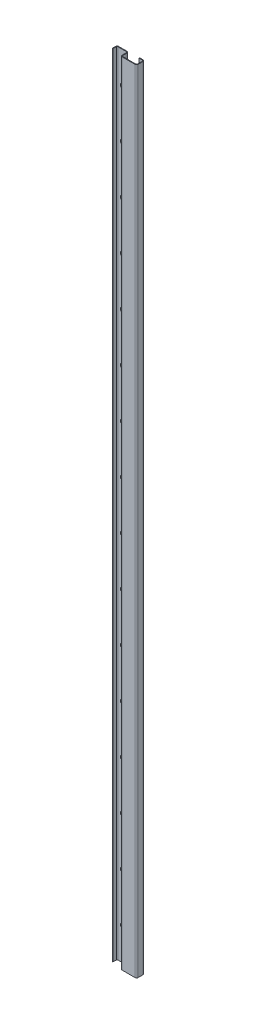
SolidWorks part; units mm, degrees
note: The reader was unsure of these and kept them because the rebuilt part matched: flange length of "Edge-Flange1", "Edge-Flange2", "Edge-Flange3", "Edge-Flange4", "Edge-Flange5".
material "Galvanized Steel"
ref_plane "Front Plane" through (0, 0, 0) normal (0, 0, 1) x (1, 0, 0)
ref_plane "Top Plane" through (0, 0, 0) normal (0, 1, 0) x (1, 0, 0)
ref_plane "Right Plane" through (0, 0, 0) normal (1, 0, 0) x (0, 0, -1)
sketch "Sketch1" plane through (0, 0, 0) normal (0, 0, 1) x (1, 0, 0)
  line L1 (18, -1240) -> (-18, -1240)
  line L2 (18, -1240) -> (18, 1240)
  line L3 (18, 1240) -> (-18, 1240)
  line L4 (-18, -1240) -> (-18, 1240)
  line L5 (18, -1240) -> (-18, 1240) construction
  line L6 (18, 1240) -> (-18, -1240) construction
  point P0 (0, 0)
  dimension "D1" = 2480
  dimension "D2" = 36
base flange "Base-Flange1" sketch "Sketch1" thickness 2 reverse thickness direction no parameters "D1"=8
edge flange "Edge-Flange1" sketch "Sketch8" flange angle 90 flange length 15 flange position material inside bend radius 2.5 thickness 2 relief rectangular parameters "D6"=10
sketch "Sketch8" plane through (-18, 0, 0) normal (-1, 0, 0) x (0, -1, 0)
  line L2 (-1240, 0) -> (-1240, 13)
  line L3 (-1240, 13) -> (1240, 13)
  line L4 (1240, 13) -> (1240, 0)
  line L7 (-1240, 0) -> (1240, 0) construction
  line L8 (-1240, 0) -> (1240, 0)
bend "EdgeBend1" bend radius 2.5 bend angle 90 parameters "D5"=1
edge flange "Edge-Flange2" sketch "Sketch11" flange angle 90 flange length 23 flange position material inside bend radius 2.5 thickness 2 parameters "D6"=10
sketch "Sketch11" plane through (18, 0, 0) normal (1, 0, 0) x (0, 1, 0)
  line L0 (-1240, 0) -> (1240, 0) construction
  line L1 (-1240, 0) -> (1240, 0)
  line L2 (-1240, 0) -> (-1240, 21)
  line L3 (-1240, 21) -> (1240, 21)
  line L4 (1240, 21) -> (1240, 0)
bend "EdgeBend2" bend radius 2.5 bend angle 90 parameters "D5"=2
edge flange "Edge-Flange3" sketch "Sketch14" flange angle 90 flange length 50 flange position material inside bend radius 2.5 thickness 2 relief rectangular parameters "D6"=10
sketch "Sketch14" plane through (18, 0, 21) normal (0, 0, 1) x (0, -1, 0)
  line L2 (-1240, 0) -> (-1240, 48)
  line L3 (-1240, 48) -> (1240, 48)
  line L4 (1240, 48) -> (1240, 0)
  line L7 (-1240, 0) -> (1240, 0) construction
  line L8 (-1240, 0) -> (1240, 0)
bend "EdgeBend3" bend radius 2.5 bend angle 90 parameters "D5"=3
edge flange "Edge-Flange4" sketch "Sketch17" flange angle 90 flange length 25 flange position material inside bend radius 2.5 thickness 2 relief rectangular parameters "D6"=10
sketch "Sketch17" plane through (66, 0, 19) normal (-1, 0, 0) x (0, 1, 0)
  line L2 (-1240, 0) -> (-1240, 23)
  line L3 (-1240, 23) -> (1240, 23)
  line L4 (1240, 23) -> (1240, 0)
  line L5 (1240, 0) -> (-1240, 0) construction
  line L6 (1240, 0) -> (-1240, 0)
bend "EdgeBend4" bend radius 2.5 bend angle 90 parameters "D5"=4
edge flange "Edge-Flange5" sketch "Sketch20" flange angle 90 flange length 15 flange position material inside bend radius 2.5 thickness 2 relief rectangular parameters "D6"=10
sketch "Sketch20" plane through (64, 0, -4) normal (0, 0, 1) x (0, 1, 0)
  line L2 (-1240, 0) -> (-1240, 13)
  line L3 (-1240, 13) -> (1240, 13)
  line L4 (1240, 13) -> (1240, 0)
  line L5 (1240, 0) -> (-1240, 0) construction
  line L6 (1240, 0) -> (-1240, 0)
bend "EdgeBend5" bend radius 2.5 bend angle 90 parameters "D5"=5
sketch "Sketch21" plane through (0, 0, 0) normal (0, 0, 1) x (1, 0, 0)
  line L0 (-18, -1240) -> (-18, 1240) construction
  line L1 (13.5, 1240) -> (-13.5, 1240) construction
  circle A0 centre (0, 1140) radius 6
  dimension "D1" = 12
  dimension "D2" = 18
  dimension "D3" = 100
extrude "Cut-Extrude1" cut sketch "Sketch21" against normal blind 10 normal cut yes
pattern_linear "LPattern1" count 16 spacing 152 along (0, -1, 0) of "Cut-Extrude1"
sketch "Bend-Lines1" [suppressed] plane through (0, 0, 0) normal (0, 1, 0) x (1, 0, 0)
sketch "Bounding-Box1" [suppressed] plane through (0, 0, 0) normal (0, 1, 0) x (1, 0, 0)
sheet metal parameters "Sheet-Metal8" thickness 2 parameters "D1"=8
flat pattern "Flat-Pattern8" [suppressed]
sketch "Bend-Lines2" plane through (0, 0, 0) normal (0, 1, 0) x (1, 0, 0)
sketch3d "Bounding-Box2" [suppressed]
  line L0 (-18, 1214, 0) -> (-18, -1214, 0) construction
  line L1 (18, 1214, 0) -> (18, -1214, 0) construction
  line L2 (-18, 1214, 0) -> (18, 1214, 0) construction
  line L3 (-18, -1214, 0) -> (18, -1214, 0) construction
sheet metal parameters "Sheet-Metal9" thickness 2 parameters "D1"=8
flat pattern "Flat-Pattern8"
sketch "Bend-Lines2" plane through (0, 0, 0) normal (0, 0, 1) x (1, 0, 0)
  line L0 (-16.2489, 1214) -> (-16.2489, -1214) construction
  line L1 (-16.2489, 1214) -> (-16.2489, -1214) construction
sketch3d "Bounding-Box2" [suppressed]
  line L0 (18, 1214, 0) -> (18, -1214, 0) construction
  line L1 (-29.4978, 1214, 0) -> (-29.4978, -1214, 0) construction
  line L2 (18, 1214, 0) -> (-29.4978, 1214, 0) construction
  line L3 (18, -1214, 0) -> (-29.4978, -1214, 0) construction
bend of the flat pattern "Flatten-<EdgeBend1>1"
sheet metal parameters "Sheet-Metal10" thickness 2 parameters "D1"=8
flat pattern "Flat-Pattern8"
sketch "Bend-Lines2" plane through (0, 0, 0) normal (0, 0, 1) x (1, 0, 0)
  line L0 (-16.2489, 1214) -> (-16.2489, -1214) construction
  line L1 (-16.2489, 1214) -> (-16.2489, -1214) construction
  line L2 (15.0686, -1214) -> (15.0686, 1214) construction
  line L3 (15.0686, -1214) -> (15.0686, 1214) construction
sketch3d "Bounding-Box2" [suppressed]
  line L0 (37.1372, 1214, 0) -> (37.1372, -1214, 0) construction
  line L1 (-29.4978, 1214, 0) -> (-29.4978, -1214, 0) construction
  line L2 (37.1372, 1214, 0) -> (-29.4978, 1214, 0) construction
  line L3 (37.1372, -1214, 0) -> (-29.4978, -1214, 0) construction
bend of the flat pattern "Flatten-<EdgeBend1>1"
bend of the flat pattern "Flatten-<EdgeBend2>1"
sheet metal parameters "Sheet-Metal11" thickness 2 parameters "D1"=8
flat pattern "Flat-Pattern8"
sketch "Bend-Lines2" plane through (0, 0, 0) normal (0, 0, 1) x (1, 0, 0)
  line L0 (-16.2489, 1214) -> (-16.2489, -1214) construction
  line L1 (-16.2489, 1214) -> (-16.2489, -1214) construction
  line L2 (15.0686, -1214) -> (15.0686, 1214) construction
  line L3 (15.0686, -1214) -> (15.0686, 1214) construction
  line L4 (35.3861, -1214) -> (35.3861, 1214) construction
  line L5 (35.3861, -1214) -> (35.3861, 1214) construction
sketch3d "Bounding-Box2" [suppressed]
  line L0 (83.635, 1214, 0) -> (83.635, -1214, 0) construction
  line L1 (-29.4978, 1214, 0) -> (-29.4978, -1214, 0) construction
  line L2 (83.635, 1214, 0) -> (-29.4978, 1214, 0) construction
  line L3 (83.635, -1214, 0) -> (-29.4978, -1214, 0) construction
bend of the flat pattern "Flatten-<EdgeBend1>1"
bend of the flat pattern "Flatten-<EdgeBend2>1"
bend of the flat pattern "Flatten-<EdgeBend3>1"
sheet metal parameters "Sheet-Metal12" thickness 2 parameters "D1"=8
flat pattern "Flat-Pattern8"
sketch "Bend-Lines2" plane through (0, 0, 0) normal (0, 0, 1) x (1, 0, 0)
  line L0 (-16.2489, 1214) -> (-16.2489, -1214) construction
  line L1 (-16.2489, 1214) -> (-16.2489, -1214) construction
  line L2 (15.0686, -1214) -> (15.0686, 1214) construction
  line L3 (15.0686, -1214) -> (15.0686, 1214) construction
  line L4 (35.3861, -1214) -> (35.3861, 1214) construction
  line L5 (35.3861, -1214) -> (35.3861, 1214) construction
  line L6 (81.8838, -1214) -> (81.8838, 1214) construction
  line L7 (81.8838, -1214) -> (81.8838, 1214) construction
sketch3d "Bounding-Box2" [suppressed]
  line L0 (105.1327, 1214, 0) -> (105.1327, -1214, 0) construction
  line L1 (-29.4978, 1214, 0) -> (-29.4978, -1214, 0) construction
  line L2 (105.1327, 1214, 0) -> (-29.4978, 1214, 0) construction
  line L3 (105.1327, -1214, 0) -> (-29.4978, -1214, 0) construction
bend of the flat pattern "Flatten-<EdgeBend1>1"
bend of the flat pattern "Flatten-<EdgeBend2>1"
bend of the flat pattern "Flatten-<EdgeBend3>1"
bend of the flat pattern "Flatten-<EdgeBend4>1"
sheet metal parameters "Sheet-Metal13" thickness 2 parameters "D1"=8
flat pattern "Flat-Pattern8"
sketch "Bend-Lines2" plane through (0, 0, 0) normal (0, 0, 1) x (1, 0, 0)
  line L0 (-16.2489, 1210) -> (-16.2489, -1210) construction
  line L1 (-16.2489, 1210) -> (-16.2489, -1210) construction
  line L2 (16.2489, -1210) -> (16.2489, 1210) construction
  line L3 (16.2489, -1210) -> (16.2489, 1210) construction
  line L4 (35.7467, -1210) -> (35.7467, 1210) construction
  line L5 (35.7467, -1210) -> (35.7467, 1210) construction
  line L6 (82.2445, -1210) -> (82.2445, 1210) construction
  line L7 (82.2445, -1210) -> (82.2445, 1210) construction
  line L8 (103.7423, -1210) -> (103.7423, 1210) construction
  line L9 (103.7423, -1210) -> (103.7423, 1210) construction
sketch3d "Bounding-Box2" [suppressed]
  line L0 (116.9911, 1210, 0) -> (116.9911, -1210, 0) construction
  line L1 (-29.4978, 1210, 0) -> (-29.4978, -1210, 0) construction
  line L2 (116.9911, 1210, 0) -> (-29.4978, 1210, 0) construction
  line L3 (116.9911, -1210, 0) -> (-29.4978, -1210, 0) construction
bend of the flat pattern "Flatten-<EdgeBend1>1"
bend of the flat pattern "Flatten-<EdgeBend2>1"
bend of the flat pattern "Flatten-<EdgeBend3>1"
bend of the flat pattern "Flatten-<EdgeBend4>1"
bend of the flat pattern "Flatten-<EdgeBend5>1"
sheet metal parameters "Sheet-Metal14" thickness 2 parameters "D1"=8
flat pattern "Flat-Pattern8"
sketch "Bend-Lines2" plane through (0, 0, 0) normal (0, 0, 1) x (1, 0, 0)
  line L0 (-16.2489, 1210) -> (-16.2489, -1210) construction
  line L1 (-16.2489, 1210) -> (-16.2489, -1210) construction
  line L2 (16.2489, -1210) -> (16.2489, 1210) construction
  line L3 (16.2489, -1210) -> (16.2489, 1210) construction
  line L4 (35.7467, -1210) -> (35.7467, 1210) construction
  line L5 (35.7467, -1210) -> (35.7467, 1210) construction
  line L6 (82.2445, -1210) -> (82.2445, 1210) construction
  line L7 (82.2445, -1210) -> (82.2445, 1210) construction
  line L8 (103.7423, -1210) -> (103.7423, 1210) construction
  line L9 (103.7423, -1210) -> (103.7423, 1210) construction
sketch3d "Bounding-Box2" [suppressed]
  line L0 (116.9911, 1210, 0) -> (116.9911, -1210, 0) construction
  line L1 (-29.4978, 1210, 0) -> (-29.4978, -1210, 0) construction
  line L2 (116.9911, 1210, 0) -> (-29.4978, 1210, 0) construction
  line L3 (116.9911, -1210, 0) -> (-29.4978, -1210, 0) construction
bend of the flat pattern "Flatten-<EdgeBend1>1"
bend of the flat pattern "Flatten-<EdgeBend2>1"
bend of the flat pattern "Flatten-<EdgeBend3>1"
bend of the flat pattern "Flatten-<EdgeBend4>1"
bend of the flat pattern "Flatten-<EdgeBend5>1"
sheet metal parameters "Sheet-Metal15" thickness 2 parameters "D1"=8
flat pattern "Flat-Pattern8"
sketch "Bend-Lines2" plane through (0, 0, 0) normal (0, 0, 1) x (1, 0, 0)
  line L0 (-16.2489, 1240) -> (-16.2489, -1240) construction
  line L1 (-16.2489, 1240) -> (-16.2489, -1240) construction
  line L2 (16.2489, -1240) -> (16.2489, 1240) construction
  line L3 (16.2489, -1240) -> (16.2489, 1240) construction
  line L4 (35.7467, -1240) -> (35.7467, 1240) construction
  line L5 (35.7467, -1240) -> (35.7467, 1240) construction
  line L6 (82.2445, -1240) -> (82.2445, 1240) construction
  line L7 (82.2445, -1240) -> (82.2445, 1240) construction
  line L8 (103.7423, -1240) -> (103.7423, 1240) construction
  line L9 (103.7423, -1240) -> (103.7423, 1240) construction
sketch3d "Bounding-Box2" [suppressed]
  line L0 (116.9911, 1240, 0) -> (116.9911, -1240, 0) construction
  line L1 (-29.4978, 1240, 0) -> (-29.4978, -1240, 0) construction
  line L2 (116.9911, 1240, 0) -> (-29.4978, 1240, 0) construction
  line L3 (116.9911, -1240, 0) -> (-29.4978, -1240, 0) construction
bend of the flat pattern "Flatten-<EdgeBend1>1"
bend of the flat pattern "Flatten-<EdgeBend2>1"
bend of the flat pattern "Flatten-<EdgeBend3>1"
bend of the flat pattern "Flatten-<EdgeBend4>1"
bend of the flat pattern "Flatten-<EdgeBend5>1"
